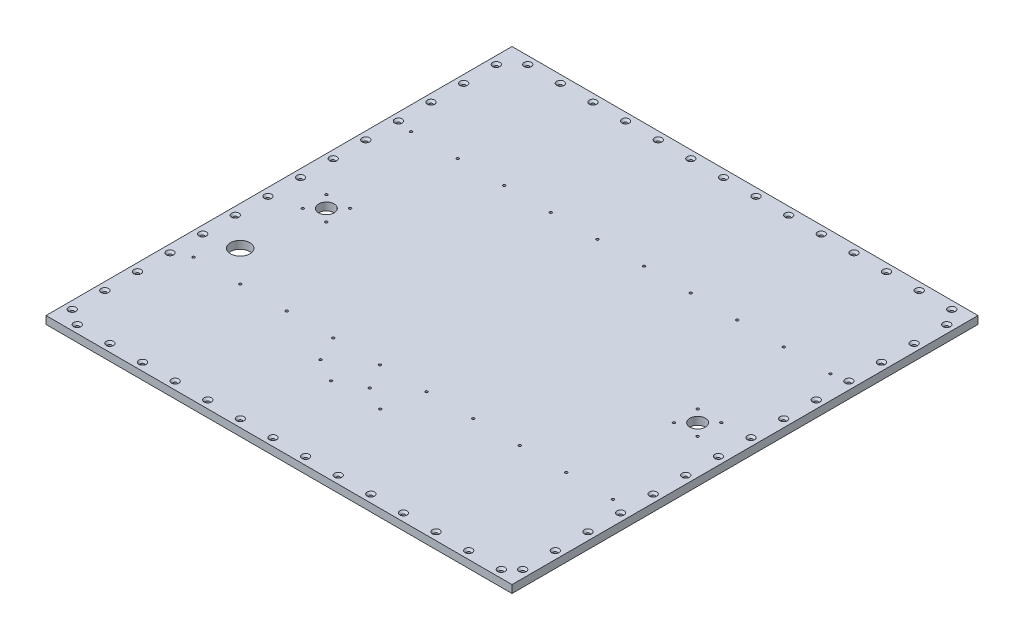
SolidWorks part; units mm, degrees
ref_plane "Płaszczyzna przednia" through (0, 0, 0) normal (0, 0, 1) x (1, 0, 0)
ref_plane "Płaszczyzna górna" through (0, 0, 0) normal (0, 1, 0) x (1, 0, 0)
ref_plane "Płaszczyzna prawa" through (0, 0, 0) normal (1, 0, 0) x (0, 0, -1)
sketch "Sketch1" plane through (0, 0, 0) normal (0, 1, 0) x (1, 0, 0)
  line L1 (0, 0) -> (600, 0)
  line L2 (0, 0) -> (0, 600)
  line L3 (0, 600) -> (600, 600)
  line L4 (600, 0) -> (600, 600)
  line L5 (0, 0) -> (600, 600) construction
  line L6 (0, 600) -> (600, 0) construction
  point P4 (300, 300)
  dimension "D1" = 600
  dimension "D2" = 600
extrude "Boss-Extrude1" add sketch "Sketch1" along normal blind 10
hole_wizard "CSK for M4 Flat Head Machine Screw1" positions "Sketch2" profile "Sketch3" countersink size "M4" standard "ANSI Metric" end condition through all
sketch "Sketch2" plane through (0, 10, 0) normal (0, 1, 0) x (1, 0, 0)
  line L0 (600, 600) -> (0, 600) construction
  line L1 (0, 600) -> (0, 0) construction
  point P0 (10, 569.75)
  point P2 (30.25, 590)
  point P20 (72.25, 590)
  point P21 (114.25, 590)
  point P22 (156.25, 590)
  point P23 (198.25, 590)
  point P24 (240.25, 590)
  point P25 (282.25, 590)
  point P26 (324.25, 590)
  point P27 (366.25, 590)
  point P28 (408.25, 590)
  point P29 (450.25, 590)
  point P30 (492.25, 590)
  point P31 (534.25, 590)
  point P32 (576.25, 590)
  point P33 (72.25, 10)
  point P34 (114.25, 10)
  point P35 (156.25, 10)
  point P36 (198.25, 10)
  point P37 (240.25, 10)
  point P38 (282.25, 10)
  point P39 (324.25, 10)
  point P40 (366.25, 10)
  point P41 (408.25, 10)
  point P42 (450.25, 10)
  point P43 (492.25, 10)
  point P44 (534.25, 10)
  point P45 (576.25, 10)
  point P46 (30.25, 10)
  point P53 (590, 569.75)
  point P54 (590, 527.75)
  point P55 (590, 485.75)
  point P56 (590, 443.75)
  point P57 (590, 401.75)
  point P58 (590, 359.75)
  point P59 (590, 317.75)
  point P60 (590, 275.75)
  point P61 (590, 233.75)
  point P62 (590, 191.75)
  point P63 (590, 149.75)
  point P64 (590, 107.75)
  point P65 (590, 65.75)
  point P66 (590, 23.75)
  point P67 (10, 527.75)
  point P68 (10, 485.75)
  point P69 (10, 443.75)
  point P70 (10, 401.75)
  point P71 (10, 359.75)
  point P72 (10, 317.75)
  point P73 (10, 275.75)
  point P74 (10, 233.75)
  point P75 (10, 191.75)
  point P76 (10, 149.75)
  point P77 (10, 107.75)
  point P78 (10, 65.75)
  point P79 (10, 23.75)
  dimension "D1" = 30.25
  dimension "D2" = 10
  dimension "D3" = 10
  dimension "D4" = 30.25
  dimension "D5" = 14
  dimension "D6" = 2
  dimension "D7" = 2
  dimension "D8" = 14
sketch "Sketch3" plane through (10, 10, -569.75) normal (1, 0, 0) x (0, 0, 1)
  line L0 (0, 0) -> (0, 10)
  line L1 (0, 10) -> (2.15, 10)
  line L2 (2.15, 10) -> (2.15, 2.55)
  line L3 (2.15, 2.55) -> (4.7, 0)
  line L5 (4.7, 0) -> (0, 0)
  line L6 (-2.15, 2.55) -> (-4.7, 0) construction
  line L11 (0, -6.35) -> (0, 107.95) construction
  dimension "Thru Hole Dia." = 4.3
  dimension "Thru Hole Depth" = 10
  dimension "Near C'Sink Dia." = 9.4
  dimension "Near C'Sink Angle" = 90
hole_wizard "CSK for M3 Flat Head Machine Screw1" positions "Sketch4" profile "Sketch6" countersink size "M3" standard "ANSI Metric" end condition through all
sketch "Sketch4" plane through (0, 0, 0) normal (0, -1, 0) x (-1, 0, 0)
  line L0 (-600, 0) -> (-600, 600) construction
  line L1 (0, 0) -> (-600, 0) construction
  line L2 (-600, 600) -> (0, 600) construction
  point P0 (-570, 160)
  point P2 (-570, 440)
  point P16 (-510, 160)
  point P17 (-510, 440)
  point P18 (-450, 160)
  point P19 (-450, 440)
  point P20 (-390, 160)
  point P21 (-390, 440)
  point P22 (-330, 160)
  point P23 (-330, 440)
  point P24 (-270, 160)
  point P25 (-270, 440)
  point P26 (-210, 160)
  point P27 (-210, 440)
  point P28 (-150, 160)
  point P29 (-150, 440)
  point P30 (-90, 160)
  point P31 (-90, 440)
  point P32 (-30, 160)
  point P33 (-30, 440)
  dimension "D1" = 30
  dimension "D2" = 160
  dimension "D3" = 30
  dimension "D4" = 160
  dimension "D5" = 10
sketch "Sketch6" plane through (570, 0, -160) normal (1, 0, 0) x (0, 0, -1)
  line L0 (0, 0) -> (0, 10)
  line L1 (0, 10) -> (1.6, 10)
  line L2 (1.6, 10) -> (1.6, 1.55)
  line L3 (1.6, 1.55) -> (3.15, 0)
  line L5 (3.15, 0) -> (0, 0)
  line L6 (-1.6, 1.55) -> (-3.15, 0) construction
  line L11 (0, -6.35) -> (0, 107.95) construction
  dimension "Thru Hole Dia." = 3.2
  dimension "Thru Hole Depth" = 10
  dimension "Near C'Sink Dia." = 6.3
  dimension "Near C'Sink Angle" = 90
sketch "Sketch7" plane through (0, 0, 0) normal (0, -1, 0) x (-1, 0, 0)
  line L0 (0, 600) -> (0, 0) construction
  line L1 (-600, 600) -> (0, 600) construction
  line L2 (-600, 0) -> (-600, 600) construction
  circle A0 centre (-61, 300) radius 10
  circle A1 centre (-539, 300) radius 10
  dimension "D2" = 20
  dimension "D3" = 300
  dimension "D4" = 20
  dimension "D5" = 61
  dimension "D6" = 300
  dimension "60" = 61
extrude "Cut-Extrude1" cut sketch "Sketch7" against normal blind 10
hole_wizard "CSK for M3 Flat Head Machine Screw2" positions "Sketch8" profile "Sketch9" countersink size "M3" standard "ANSI Metric" end condition through all
sketch "Sketch8" plane through (0, 0, 0) normal (0, -1, 0) x (-1, 0, 0)
  line L1 (0, 600) -> (0, 0) construction
  line L2 (-20, 600) -> (-580, 600) construction
  point P0 (-45.75, 315.25)
  point P2 (-76.25, 315.25)
  point P4 (-76.25, 284.75)
  point P6 (-45.75, 284.75)
  dimension "D1" = 30.5
  dimension "D2" = 45.75
  dimension "D3" = 30.5
  dimension "D4" = 284.75
sketch "Sketch9" plane through (45.75, 0, -315.25) normal (1, 0, 0) x (0, 0, -1)
  line L0 (0, 0) -> (0, 10)
  line L1 (0, 10) -> (1.6, 10)
  line L2 (1.6, 10) -> (1.6, 1.55)
  line L3 (1.6, 1.55) -> (3.15, 0)
  line L5 (3.15, 0) -> (0, 0)
  line L6 (-1.6, 1.55) -> (-3.15, 0) construction
  line L11 (0, -6.35) -> (0, 107.95) construction
  dimension "Thru Hole Dia." = 3.2
  dimension "Thru Hole Depth" = 10
  dimension "Near C'Sink Dia." = 6.3
  dimension "Near C'Sink Angle" = 90
hole_wizard "CSK for M3 Flat Head Machine Screw3" positions "Sketch10" profile "Sketch11" countersink size "M3" standard "ANSI Metric" end condition through all
sketch "Sketch10" plane through (0, 0, 0) normal (0, -1, 0) x (-1, 0, 0)
  line L0 (-600, 0) -> (-600, 600) construction
  line L3 (-20, 600) -> (-580, 600) construction
  point P0 (-523.75, 315.25)
  point P2 (-554.25, 315.25)
  point P4 (-554.25, 284.75)
  point P6 (-523.75, 284.75)
  dimension "D1" = 45.75
  dimension "D2" = 284.75
  dimension "D3" = 30.5
  dimension "D4" = 30.5
sketch "Sketch11" plane through (523.75, 0, -315.25) normal (1, 0, 0) x (0, 0, -1)
  line L0 (0, 0) -> (0, 10)
  line L1 (0, 10) -> (1.6, 10)
  line L2 (1.6, 10) -> (1.6, 1.55)
  line L3 (1.6, 1.55) -> (3.15, 0)
  line L5 (3.15, 0) -> (0, 0)
  line L6 (-1.6, 1.55) -> (-3.15, 0) construction
  line L11 (0, -6.35) -> (0, 107.95) construction
  dimension "Thru Hole Dia." = 3.2
  dimension "Thru Hole Depth" = 10
  dimension "Near C'Sink Dia." = 6.3
  dimension "Near C'Sink Angle" = 90
hole_wizard "CSK for M3 Flat Head Machine Screw4" positions "Sketch12" profile "Sketch13" countersink size "M3" standard "ANSI Metric"
sketch "Sketch12" plane through (0, 0, 0) normal (0, -1, 0) x (-1, 0, 0)
  line L0 (-600, 580) -> (-600, 20) construction
  line L1 (-20, 0) -> (-580, 0) construction
  point P0 (-549.5, 118.5)
  point P2 (-549.5, 68.8)
  point P4 (-397.5, 118.5)
  point P6 (-397.5, 68.8)
  dimension "D1" = 50.5
  dimension "D2" = 118.5
  dimension "D3" = 49.7
  dimension "D4" = 152
sketch "Sketch13" plane through (549.5, 0, -118.5) normal (1, 0, 0) x (0, 0, -1)
  line L0 (0, 0) -> (0, 6.9614)
  line L1 (0, 6.9614) -> (1.6, 6)
  line L2 (1.6, 6) -> (1.6, 1.55)
  line L3 (1.6, 1.55) -> (3.15, 0)
  line L5 (3.15, 0) -> (0, 0)
  line L6 (-1.6, 1.55) -> (-3.15, 0) construction
  line L10 (0, 6.9614) -> (-1.6, 6) construction
  line L11 (0, -6.35) -> (0, 107.95) construction
  dimension "Hole Dia." = 3.2
  dimension "Hole Depth" = 6
  dimension "Near C'Sink Dia." = 6.3
  dimension "Near C'Sink Angle" = 90
  dimension "Drill Angle" = 118
sketch "Sketch14" plane through (0, 0, 0) normal (0, -1, 0) x (1, 0, 0)
  line L0 (0, 0) -> (600, 0) construction
  line L1 (600, -580) -> (600, -20) construction
  circle A0 centre (425, -42) radius 4
  dimension "D1" = 42
  dimension "D2" = 175
  dimension "D3" = 8
extrude "Cut-Extrude2" cut sketch "Sketch14" against normal blind 5
sketch "Sketch15" plane through (0, 0, 0) normal (0, -1, 0) x (-1, 0, 0)
  line L0 (-20, 0) -> (-580, 0) construction
  line L1 (0, 20) -> (0, 580) construction
  circle A0 centre (-175, 42) radius 4
  dimension "D1" = 42
  dimension "D2" = 8
  dimension "D3" = 175
extrude "Cut-Extrude3" cut sketch "Sketch15" against normal blind 5
sketch "Sketch16" plane through (0, 10, 0) normal (0, 1, 0) x (1, 0, 0)
  line L0 (0, 0) -> (0, 600) construction
  line L1 (0, 0) -> (600, 0) construction
  circle A0 centre (50, 200) radius 12.5
  dimension "D1" = 25
  dimension "D2" = 50
  dimension "D3" = 200
extrude "Cut-Extrude4" cut sketch "Sketch16" against normal blind 10
hole_wizard "Ø3.0mm Dowel Hole1" positions "Sketch17" profile "Sketch19" hole size "Ø3.0" standard "ANSI Metric" end condition through all
sketch "Sketch17" plane through (0, 10, 0) normal (0, 1, 0) x (1, 0, 0)
  point P0 (319.5, 110.75)
  point P3 (289.25, 127.5)
  point P6 (256.25, 110.75)
  point P9 (226, 127.5)
sketch "Sketch19" plane through (319.5, 10, -110.75) normal (1, 0, 0) x (0, 0, 1)
  line L0 (0, 0) -> (0, 10)
  line L1 (0, 10) -> (1.6, 10)
  line L2 (1.6, 10) -> (1.6, 0)
  line L5 (1.6, 0) -> (0, 0)
  line L11 (0, -6.35) -> (0, 107.95) construction
  dimension "Thru Hole Dia." = 3.2
  dimension "Thru Hole Depth" = 10
